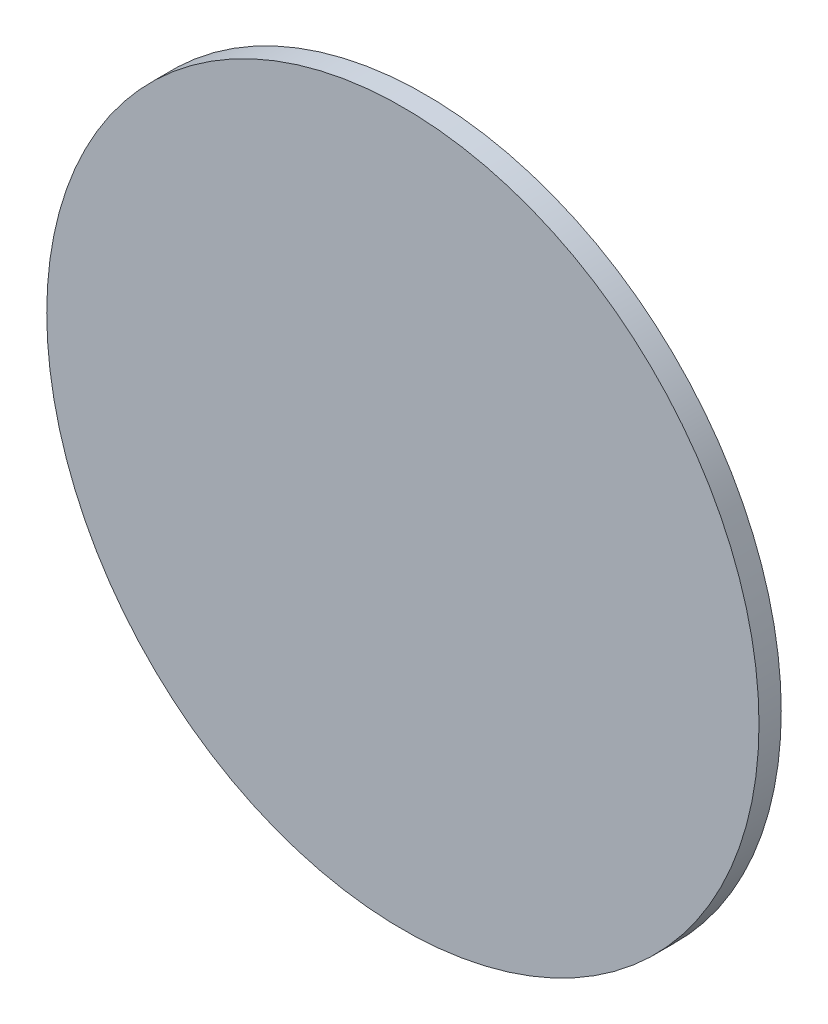
SolidWorks part; units mm, degrees
material "Ceramic Porcelain"
ref_plane "Front Plane" through (0, 0, 0) normal (0, 0, 1) x (1, 0, 0)
ref_plane "Top Plane" through (0, 0, 0) normal (0, 1, 0) x (1, 0, 0)
ref_plane "Right Plane" through (0, 0, 0) normal (1, 0, 0) x (0, 0, -1)
ref_plane "Plane1" through (0, 0, 0) normal (0, 0, -1) x (-1, 0, 0)
sketch "Sketch1" plane through (0, 0, 0) normal (0, 0, -1) x (-1, 0, 0)
  line L2 (-12.5, 0) -> (12.5, 0) construction
  line L3 (0, 16) -> (0, -12.5) construction
  circle A28 centre (0, 0) radius 16
  dimension "D1" = 32
extrude "Boss-Extrude1" add sketch "Sketch1" against normal blind 1
ref_axis "Axis1" through (0, 13.1424, 0) along (0, -1, 0)
ref_axis "Axis2" through (-17.8818, 0, 0) along (1, 0, 0)
ref_axis "Axis3" through (-20.9, 0, 1) along (1, 0, 0)
ref_axis "Axis4" through (0, 20.9, 1) along (0, -1, 0)
